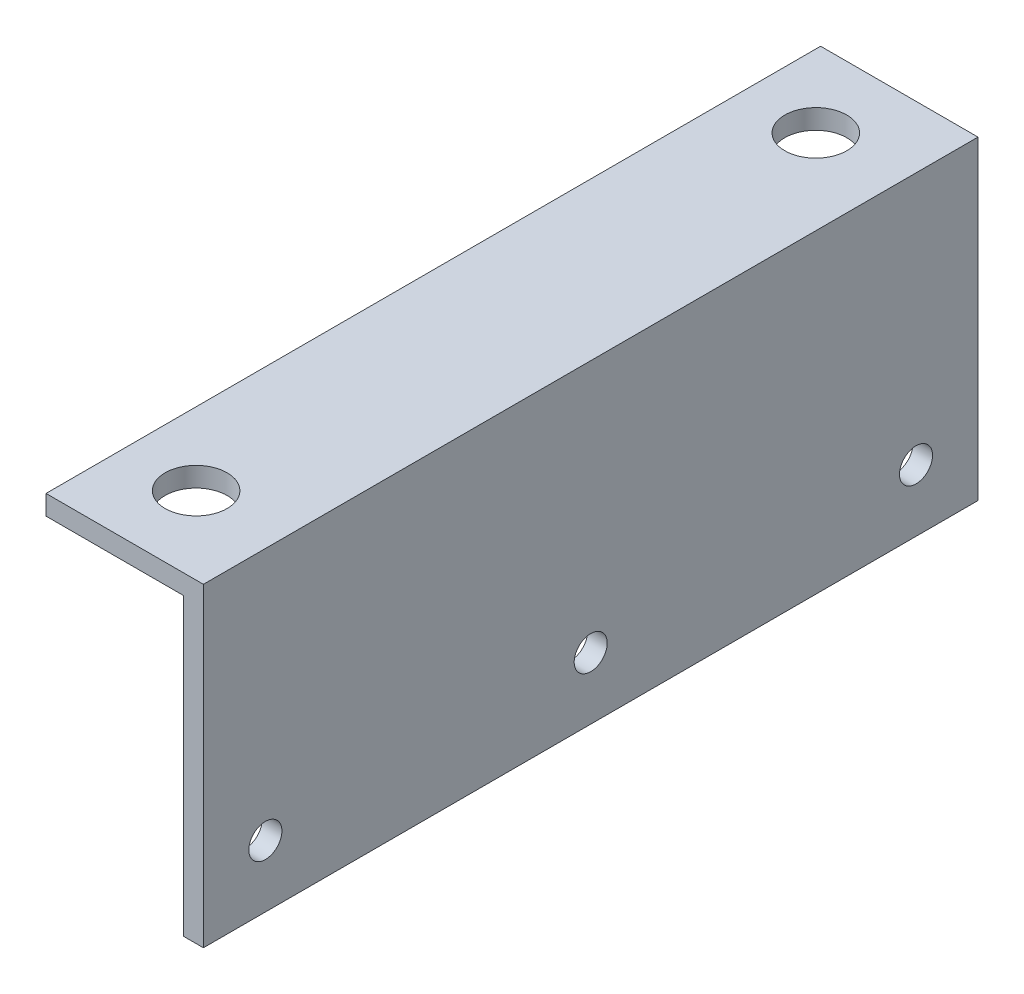
SolidWorks part; units mm, degrees
ref_plane "Front Plane" through (0, 0, 0) normal (0, 0, 1) x (1, 0, 0)
ref_plane "Top Plane" through (0, 0, 0) normal (0, 1, 0) x (1, 0, 0)
ref_plane "Right Plane" through (0, 0, 0) normal (1, 0, 0) x (0, 0, -1)
sketch "Sketch1" plane through (0, 0, 0) normal (0, 0, 1) x (1, 0, 0)
  line L0 (0, 0) -> (0, 50.8)
  line L1 (0, 50.8) -> (-25.4, 50.8)
  line L2 (-3.175, 0) -> (-3.175, 47.625)
  line L3 (-3.175, 47.625) -> (-25.4, 47.625)
  line L4 (-25.4, 50.8) -> (-25.4, 47.625)
  line L5 (-3.175, 0) -> (0, 0)
  dimension "D1" = 25.4
  dimension "D2" = 50.8
  dimension "D3" = 3.175
extrude "Boss-Extrude1" add sketch "Sketch1" along normal blind 125
sketch "Sketch2" plane through (0, 0, 0) normal (1, 0, 0) x (0, 0, -1)
  line L0 (-125, 10) -> (0, 10) construction
  line L1 (-125, 0) -> (-125, 50.8) construction
  line L2 (0, 0) -> (0, 50.8) construction
  line L3 (-125, 0) -> (0, 0) construction
  circle A0 centre (-115, 10) radius 2.665
  circle A1 centre (-10, 10) radius 2.665
  circle A2 centre (-62.5, 10) radius 2.665
  dimension "D2" = 5.33
  dimension "D3" = 10
  dimension "D4" = 10
  dimension "D1" = 10
extrude "Cut-Extrude1" cut sketch "Sketch2" against normal up to next
sketch "Sketch3" plane through (0, 50.8, 0) normal (0, 1, 0) x (1, 0, 0)
  line L0 (0, -62.5) -> (-25.4, -62.5) construction
  line L1 (0, -125) -> (0, 0) construction
  line L2 (-25.4, -125) -> (-25.4, 0) construction
  arc A0 (-13.675, -7.5) -> (-13.675, -17.5) centre (-13.675, -12.5) ccw construction
  arc A1 (-13.675, -7.5) -> (-13.675, -17.5) centre (-13.675, -12.5) ccw
  circle A2 centre (-13.675, -12.5) radius 5
  circle A3 centre (-13.675, -112.5) radius 5
  point P12 (0, 0)
extrude "Cut-Extrude2" cut sketch "Sketch3" against normal up to next contours A3 | A1 A2 region at (-13.675, 50.8, 12.5) region at (-13.675, 50.8, 112.5)
